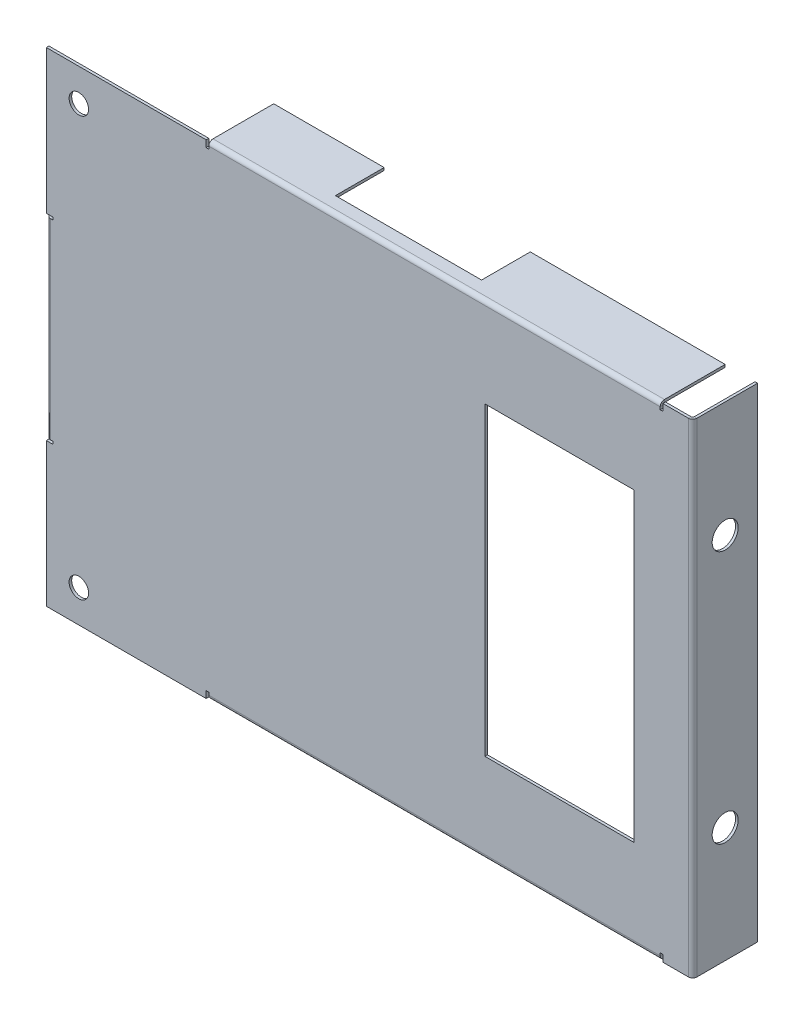
SolidWorks part; units mm, degrees
note: The reader was unsure of these and kept them because the rebuilt part matched: flange length of "边线-法兰1", "边线-法兰3", "边线-法兰4", "边线-法兰5".
ref_plane "前视基准面" through (0, 0, 0) normal (0, 0, 1) x (1, 0, 0)
ref_plane "上视基准面" through (0, 0, 0) normal (0, 1, 0) x (1, 0, 0)
ref_plane "右视基准面" through (0, 0, 0) normal (1, 0, 0) x (0, 0, -1)
sketch "草图1" plane through (0, 0, 0) normal (0, 0, 1) x (1, 0, 0)
  line L0 (99.5, 0) -> (-117.273, 0) construction
  line L1 (-99.5, 74.5) -> (99.5, 74.5)
  line L2 (-99.5, 74.5) -> (-99.5, -74.5)
  line L3 (-99.5, -74.5) -> (99.5, -74.5)
  line L4 (99.5, 74.5) -> (99.5, -74.5)
  line L5 (-99.5, 74.5) -> (99.5, -74.5) construction
  line L6 (-99.5, -74.5) -> (99.5, 74.5) construction
  line L7 (81.5, -47) -> (35.5, -47)
  line L8 (81.5, -47) -> (81.5, 47)
  line L9 (81.5, 47) -> (35.5, 47)
  line L10 (35.5, -47) -> (35.5, 47)
  circle A0 centre (-89.5, 64.5) radius 3
  circle A1 centre (-89.5, -64.5) radius 3
  point P0 (0, 0)
  dimension "D7" = 6
  dimension "D1" = 199
  dimension "D2" = 149
  dimension "D3" = 10
  dimension "D4" = 10
  dimension "D5" = 10
  dimension "D6" = 10
  dimension "D8" = 18
  dimension "D9" = 46
  dimension "D10" = 94
base flange "基体-法兰1" sketch "草图1" thickness 0.8 reverse thickness direction no parameters "D1"=0.5
edge flange "边线-法兰1" sketch "草图8" flange angle 90 flange length 20 flange position material inside bend radius 0.5 thickness 0.8 relief rectangular parameters "D6"=10
sketch "草图8" plane through (-99.5, 0, -0.8) normal (-1, 0, 0) x (0, 1, 0)
  line L0 (74.5, 0) -> (-74.5, 0) construction
  line L1 (29.5, 0) -> (-29.5, 0)
  line L2 (-29.5, 0) -> (-29.5, 19.2)
  line L3 (-29.5, 19.2) -> (29.5, 19.2)
  line L4 (29.5, 19.2) -> (29.5, 0)
  line L5 (-74.5, 0) -> (-74.5, -0.8) construction
  line L6 (74.5, -0.8) -> (-74.5, -0.8) construction
  line L7 (74.5, 0) -> (74.5, -0.8) construction
  dimension "D1" = 45
  dimension "D2" = 20
  dimension "D3" = 45
bend "边线折弯1" bend radius 0.5 bend angle 90 parameters "D5"=1
edge flange "边线-法兰3" sketch "草图14" flange angle 90 flange length 20 flange position material inside bend radius 0.5 thickness 0.8 relief rectangular parameters "D6"=10
sketch "草图14" plane through (0, -74.5, -0.8) normal (0, -1, 0) x (-1, 0, 0)
  line L0 (99.5, 0) -> (-99.5, 0) construction
  line L1 (49.5, 0) -> (-89.5, 0)
  line L2 (-89.5, 0) -> (-89.5, 19.2)
  line L3 (-89.5, 19.2) -> (-29.5, 19.2)
  line L4 (49.5, 19.2) -> (49.5, 0)
  line L5 (99.5, 0) -> (99.5, -0.8) construction
  line L6 (-99.5, 0) -> (-99.5, -0.8) construction
  line L7 (15.5, 19.2) -> (49.5, 19.2)
  line L8 (99.5, -0.8) -> (-99.5, -0.8) construction
  line L9 (15.5, 19.2) -> (15.5, 4.2)
  line L10 (15.5, 4.2) -> (-29.5, 4.2)
  line L11 (-29.5, 19.2) -> (-29.5, 4.2)
  dimension "D1" = 50
  dimension "D2" = 10
  dimension "D3" = 45
  dimension "D4" = 5
  dimension "D5" = 60
  dimension "D6" = 20
bend "边线折弯3" bend radius 0.5 bend angle 90 parameters "D5"=3
edge flange "边线-法兰4" sketch "草图17" flange angle 90 flange length 20 flange position material inside bend radius 0.5 thickness 0.8 relief rectangular parameters "D6"=10
sketch "草图17" plane through (0, 74.5, -0.8) normal (0, 1, 0) x (1, 0, 0)
  line L0 (99.5, 0) -> (-99.5, 0) construction
  line L1 (89.5, 0) -> (-49.5, 0)
  line L2 (-49.5, 0) -> (-49.5, 19.2)
  line L3 (-49.5, 19.2) -> (-15.5, 19.2)
  line L4 (89.5, 19.2) -> (89.5, 0)
  line L5 (-99.5, 0) -> (-99.5, -0.8) construction
  line L6 (99.5, 0) -> (99.5, -0.8) construction
  line L7 (29.5, 19.2) -> (89.5, 19.2)
  line L8 (99.5, -0.8) -> (-99.5, -0.8) construction
  line L9 (29.5, 19.2) -> (29.5, 4.2)
  line L10 (29.5, 4.2) -> (-15.5, 4.2)
  line L11 (-15.5, 19.2) -> (-15.5, 4.2)
  dimension "D1" = 50
  dimension "D2" = 10
  dimension "D3" = 20
  dimension "D4" = 5
  dimension "D5" = 45
  dimension "D6" = 60
bend "边线折弯4" bend radius 0.5 bend angle 90 parameters "D5"=4
edge flange "边线-法兰5" sketch "草图20" flange angle 90 flange length 20 flange position material inside bend radius 0.5 thickness 0.8 relief rectangular parameters "D6"=10
sketch "草图20" plane through (99.5, 0, -0.8) normal (1, 0, 0) x (0, -1, 0)
  line L0 (74.5, 0) -> (-74.5, 0) construction
  line L1 (74.5, 0) -> (-74.5, 0)
  line L2 (-74.5, 0) -> (-74.5, 19.2)
  line L3 (-74.5, 19.2) -> (74.5, 19.2)
  line L4 (74.5, 19.2) -> (74.5, 0)
bend "边线折弯5" bend radius 0.5 bend angle 90 parameters "D5"=5
sketch "草图21" plane through (99.5, 0, 0) normal (1, 0, 0) x (0, 0, -1)
  line L0 (0, 0) -> (25.289, 0) construction
  line L1 (20, -74.5) -> (20, 74.5) construction
  circle A0 centre (10, -39) radius 4
  circle A1 centre (10, 39) radius 4
  dimension "D3" = 8
  dimension "D1" = 78
  dimension "D2" = 10
extrude "切除-拉伸1" cut sketch "草图21" against normal through all normal cut yes
sketch "折弯-线1" plane through (0, 0, 0) normal (0, 1, 0) x (1, 0, 0)
sketch "边界框1" plane through (0, 0, 0) normal (0, 1, 0) x (1, 0, 0)
sheet metal parameters "钣金1" thickness 0.8 parameters "D1"=0.5
flat pattern "平板型式1" [suppressed]
sketch "折弯-线2" plane through (0, 0, 0) normal (0, 1, 0) x (1, 0, 0)
sketch "边界框2" [suppressed] plane through (0, 0, 0) normal (0, 1, 0) x (1, 0, 0)
sheet metal parameters "钣金2" thickness 0.8 parameters "D1"=0.5
flat pattern "平板型式1" [suppressed]
sketch "折弯-线2" plane through (0, 0, 0) normal (0, 1, 0) x (1, 0, 0)
sketch "边界框2" [suppressed] plane through (0, 0, 0) normal (0, 1, 0) x (1, 0, 0)
bend of the flat pattern "展开-<边线折弯1>1"
sheet metal parameters "钣金4" thickness 0.8 parameters "D1"=0.5
flat pattern "平板型式1" [suppressed]
sketch "折弯-线2" plane through (0, 0, 0) normal (0, 1, 0) x (1, 0, 0)
sketch "边界框2" [suppressed] plane through (0, 0, 0) normal (0, 1, 0) x (1, 0, 0)
bend of the flat pattern "展开-<边线折弯1>1"
bend of the flat pattern "展开-<边线折弯3>1"
sheet metal parameters "钣金5" thickness 0.8 parameters "D1"=0.5
flat pattern "平板型式1" [suppressed]
sketch "折弯-线2" plane through (0, 0, 0) normal (0, 1, 0) x (1, 0, 0)
sketch "边界框2" [suppressed] plane through (0, 0, 0) normal (0, 1, 0) x (1, 0, 0)
bend of the flat pattern "展开-<边线折弯1>1"
bend of the flat pattern "展开-<边线折弯3>1"
bend of the flat pattern "展开-<边线折弯4>1"
sheet metal parameters "钣金6" thickness 0.8 parameters "D1"=0.5
flat pattern "平板型式1" [suppressed]
sketch "折弯-线2" plane through (0, 0, 0) normal (0, 1, 0) x (1, 0, 0)
sketch "边界框2" [suppressed] plane through (0, 0, 0) normal (0, 1, 0) x (1, 0, 0)
bend of the flat pattern "展开-<边线折弯1>1"
bend of the flat pattern "展开-<边线折弯3>1"
bend of the flat pattern "展开-<边线折弯4>1"
bend of the flat pattern "展开-<边线折弯5>1"
sheet metal parameters "钣金7" thickness 0.8 parameters "D1"=0.5
flat pattern "平板型式1" [suppressed]
sketch "折弯-线2" plane through (0, 0, 0) normal (0, 1, 0) x (1, 0, 0)
sketch "边界框2" [suppressed] plane through (0, 0, 0) normal (0, 1, 0) x (1, 0, 0)
bend of the flat pattern "展开-<边线折弯1>1"
bend of the flat pattern "展开-<边线折弯3>1"
bend of the flat pattern "展开-<边线折弯4>1"
bend of the flat pattern "展开-<边线折弯5>1"
